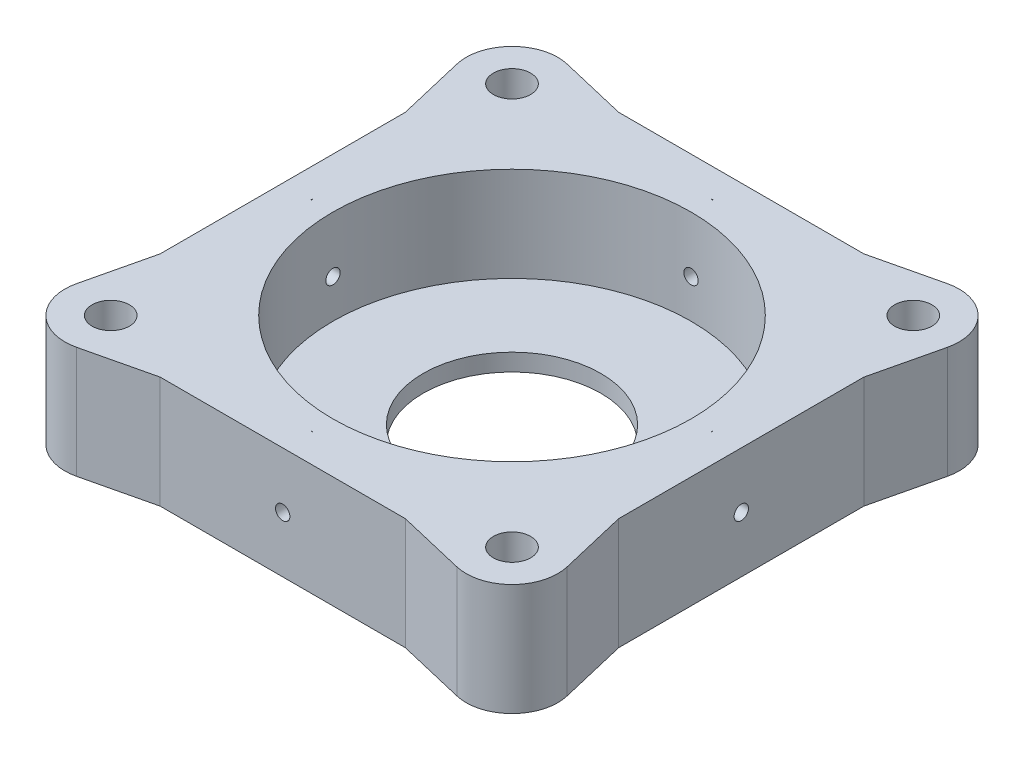
SolidWorks part; units mm, degrees
ref_plane "Front Plane" through (0, 0, 0) normal (0, 0, 1) x (1, 0, 0)
ref_plane "Top Plane" through (0, 0, 0) normal (0, 1, 0) x (1, 0, 0)
ref_plane "Right Plane" through (0, 0, 0) normal (1, 0, 0) x (0, 0, -1)
sketch "Sketch1" plane through (0, 0, 0) normal (0, 1, 0) x (1, 0, 0)
  line L0 (0, 35) -> (0, -35) construction
  line L1 (35, -35) -> (-35, -35)
  line L2 (35, -35) -> (35, 35)
  line L3 (35, 35) -> (-35, 35)
  line L4 (-35, -35) -> (-35, 35)
  line L5 (35, -35) -> (-35, 35) construction
  line L6 (35, 35) -> (-35, -35) construction
  line L7 (-35, 0) -> (35, 0) construction
  line L8 (-33.1578, 42.785) -> (7.8292, 33.0863)
  line L9 (-42.785, 33.1578) -> (-33.0863, -7.8292)
  line L10 (42.785, 33.1578) -> (33.0863, -7.8292)
  line L11 (33.1578, 42.785) -> (-7.8292, 33.0863)
  line L12 (-42.785, -33.1578) -> (-33.0863, 7.8292)
  line L13 (-33.1578, -42.785) -> (7.8292, -33.0863)
  line L14 (33.1578, -42.785) -> (-7.8292, -33.0863)
  line L15 (42.785, -33.1578) -> (33.0863, 7.8292)
  line L17 (40, -40) -> (-40, -40)
  line L18 (40, -40) -> (40, 40)
  line L19 (40, 40) -> (-40, 40)
  line L20 (-40, -40) -> (-40, 40)
  line L21 (40, -40) -> (-40, 40) construction
  line L22 (40, 40) -> (-40, -40) construction
  circle A0 centre (0, 0) radius 15.5
  circle A1 centre (0, 0) radius 34
  circle A2 centre (-35, 35) radius 3.25
  circle A3 centre (0, 0) radius 40
  circle A4 centre (-35, 35) radius 8
  circle A5 centre (35, 35) radius 3.25
  circle A6 centre (35, 35) radius 8
  circle A7 centre (-35, -35) radius 3.25
  circle A8 centre (-35, -35) radius 8
  circle A9 centre (35, -35) radius 3.25
  circle A10 centre (35, -35) radius 8
  dimension "D1" = 31
  dimension "D2" = 68
  dimension "D3" = 6.5
  dimension "D5" = 80
  dimension "D4" = 16
  dimension "D6" = 70
extrude "Boss-Extrude1" add sketch "Sketch1" along normal blind 19.5 contours L19 A4 L20 | L3 A4 L19 L20 L4 A2 | L4 A4 L3 A2 | A4 L9 L20 | A4 L20 L9 A3 L4 | A3 L9 L20 | L4 A3 L9 | L9 A3 L12 L4 | A3 L20 L12 | L12 A3 L4 | L20 A8 L4 A3 L12 | L12 A8 L20 | A8 L17 L20 | A8 L20 L17 L1 A7 L4 | A8 L4 A7 L1 | L4 A8 L1 A3 | L4 A3 L1 L13 L14 A1 L9 L12 | L3 A3 L4 L9 L12 A1 L11 L8 | A1 L12 L9 | A4 L4 A3 L3 | A4 L3 A3 L8 L19 | A4 L19 L8 | A3 L19 L8 | L8 A3 L3 | L11 A3 L8 L3 | A1 L8 L11 | L3 A3 L11 | L2 A3 L3 L11 L8 A1 L15 L10 | L3 A6 L19 L11 A3 | A3 L11 L19 | L19 A6 L11 | L2 A6 L3 A3 | A6 L2 A5 L3 | A6 L3 A5 L2 L18 L19 | A6 L19 L18 | L10 A6 L18 | L18 A6 L2 A3 L10 | A3 L18 L10 | L10 A3 L2 | L15 A3 L10 L2 | A3 L15 L18 | L2 A3 L15 | A1 L10 L15 | L1 A3 L2 L15 L10 A1 L13 L14 | A10 L18 L15 A3 L2 | A10 L15 L18 | A10 L2 A3 L1 | L18 A10 L2 A9 L1 L17 | L2 A10 L1 A9 | A10 L18 L17 | A10 L17 L14 | A10 L1 A3 L14 L17 | L14 A3 L1 | A3 L17 L14 | A3 L14 L1 L13 | A1 L14 L13 | L1 A3 L13 | A3 L13 L17 | L1 A8 L17 L13 A3 | L17 A8 L13 | A1 A0 region at (-27.625, 0, 37.5886) region at (-28.9419, 0, 28.9419) region at (-31.2062, 0, 31.2062) region at (-21.8672, 0, 37.555) region at (-24.6184, 0, 24.6184) region at (-10.9152, 0, 35.995) region at (-37.555, 0, 21.8672) region at (-30.8311, 0, 41.5907) region at (-27.2274, 0, 40.8217) region at (0, 0, 37.8149) region at (-35.995, 0, 10.9152) region at (-12.614, 0, 39.3478) region at (-40.8217, 0, 27.2274) region at (24.6184, 0, 24.6184) region at (10.9152, 0, 35.995) region at (0, 0, 34.191) region at (-37.8149, 0, 0) region at (-39.3478, 0, 12.614) region at (12.614, 0, 39.3478) region at (28.9419, 0, 28.9419) region at (21.8672, 0, 37.555) region at (0, 0, 33.0383) region at (-35.995, 0, -10.9152) region at (-24.6184, 0, -24.6184) region at (-34.191, 0, 0) region at (-39.3478, 0, -12.614) region at (27.2274, 0, 40.8217) region at (31.2062, 0, 31.2062) region at (29.375, 0, 35.1838) region at (37.555, 0, 21.8672) region at (35.995, 0, 10.9152) region at (34.191, 0, 0) region at (-37.555, 0, -21.8672) region at (-28.9419, 0, -28.9419) region at (-40.8217, 0, -27.2274) region at (30.8311, 0, 41.5907) region at (37.8149, 0, 0) region at (39.3478, 0, 12.614) region at (24.6184, 0, -24.6184) region at (-37.5886, 0, -27.625) region at (-31.2062, 0, -31.2062) region at (-10.9152, 0, -35.995) region at (-21.8672, 0, -37.555) region at (0, 0, -34.191) region at (-40.5144, 0, -40.5144) region at (40.8217, 0, 27.2274) region at (35.995, 0, -10.9152) region at (39.3478, 0, -12.614) region at (0, 0, -37.8149) region at (-12.614, 0, -39.3478) region at (-27.2274, 0, -40.8217) region at (28.9419, 0, -28.9419) region at (37.555, 0, -21.8672) region at (40.8217, 0, -27.2274) region at (10.9152, 0, -35.995) region at (12.614, 0, -39.3478) region at (31.2062, 0, -31.2062) region at (35.1838, 0, -29.375) region at (21.8672, 0, -37.555) region at (41.5907, 0, -30.8311)
sketch "Sketch2" plane through (0, 19.5, 0) normal (0, 1, 0) x (1, 0, 0)
  circle A0 centre (0, 0) radius 31.25
  dimension "D1" = 62.5
extrude "Cut-Extrude1" cut sketch "Sketch2" against normal blind 16.5
sketch "Sketch3" plane through (0, 0, 0) normal (0, -1, 0) x (1, 0, 0)
  circle A0 centre (-35, 35) radius 5.25
  circle A1 centre (35, 35) radius 5.25
  circle A2 centre (35, -35) radius 5.25
  circle A3 centre (-35, -35) radius 5.25
  dimension "D1" = 10.5
extrude "Cut-Extrude2" cut sketch "Sketch3" against normal blind 6
sketch "Sketch4" plane through (0, 0, 40) normal (0, 0, 1) x (1, 0, 0)
  line L0 (0, 0) -> (0, 19.5) construction
  line L1 (21.3883, 0) -> (-21.3883, 0) construction
  line L2 (21.3883, 19.5) -> (-21.3883, 19.5) construction
  circle A0 centre (0, 9.75) radius 1.25
  dimension "D1" = 2.5
extrude "Cut-Extrude3" cut sketch "Sketch4" against normal up to surface (80 mm away) up to face at (0, 9.75, -40)
sketch "Sketch5" plane through (40, 0, 0) normal (1, 0, 0) x (0, 0, -1)
  line L0 (0, 0) -> (0, 19.5) construction
  line L1 (-21.3883, 19.5) -> (21.3883, 19.5) construction
  circle A0 centre (0, 9.75) radius 1.25
  dimension "D1" = 2.5
extrude "Cut-Extrude4" cut sketch "Sketch5" against normal up to surface (80 mm away) up to face at (-40, 9.75, 0)
sketch "Sketch6" [suppressed] plane through (0, 19.5, 0) normal (0, 1, 0) x (1, 0, 0)
  line L12 (21.3883, -40) -> (33.1578, -42.785)
  line L13 (42.785, -33.1578) -> (40, -21.3883)
  line L14 (40, -21.3883) -> (40, 21.3883)
  line L15 (40, 21.3883) -> (42.785, 33.1578)
  line L16 (33.1578, 42.785) -> (21.3883, 40)
  line L17 (21.3883, 40) -> (-21.3883, 40)
  line L18 (-21.3883, 40) -> (-33.1578, 42.785)
  line L19 (-42.785, 33.1578) -> (-40, 21.3883)
  line L20 (-40, 21.3883) -> (-40, -21.3883)
  line L21 (-40, -21.3883) -> (-42.785, -33.1578)
  line L22 (-33.1578, -42.785) -> (-21.3883, -40)
  line L23 (-21.3883, -40) -> (21.3883, -40)
  line L24 (21.3883, -40) -> (33.1578, -42.785)
  line L25 (42.785, -33.1578) -> (40, -21.3883)
  line L26 (40, -21.3883) -> (40, 21.3883)
  line L27 (40, 21.3883) -> (42.785, 33.1578)
  line L28 (33.1578, 42.785) -> (21.3883, 40)
  line L29 (21.3883, 40) -> (-21.3883, 40)
  line L30 (-21.3883, 40) -> (-33.1578, 42.785)
  line L31 (-42.785, 33.1578) -> (-40, 21.3883)
  line L32 (-40, 21.3883) -> (-40, -21.3883)
  line L33 (-40, -21.3883) -> (-42.785, -33.1578)
  line L34 (-33.1578, -42.785) -> (-21.3883, -40)
  line L35 (-21.3883, -40) -> (21.3883, -40)
  circle A0 centre (0, 0) radius 31.25 construction
  circle A1 centre (35, 35) radius 3.25 construction
  circle A2 centre (-35, 35) radius 3.25 construction
  circle A3 centre (35, -35) radius 3.25 construction
  arc A4 (33.1578, -42.785) -> (42.785, -33.1578) centre (35, -35) ccw
  arc A5 (42.785, 33.1578) -> (33.1578, 42.785) centre (35, 35) ccw
  arc A6 (-33.1578, 42.785) -> (-42.785, 33.1578) centre (-35, 35) ccw
  arc A7 (-42.785, -33.1578) -> (-33.1578, -42.785) centre (-35, -35) ccw
  arc A8 (33.1578, -42.785) -> (42.785, -33.1578) centre (35, -35) ccw
  arc A9 (42.785, 33.1578) -> (33.1578, 42.785) centre (35, 35) ccw
  arc A10 (-33.1578, 42.785) -> (-42.785, 33.1578) centre (-35, 35) ccw
  arc A11 (-42.785, -33.1578) -> (-33.1578, -42.785) centre (-35, -35) ccw
  circle A12 centre (-35, -35) radius 3.25 construction
  circle A13 centre (0, 0) radius 31.25
  circle A14 centre (35, 35) radius 3.25
  circle A15 centre (-35, 35) radius 3.25
  circle A16 centre (35, -35) radius 3.25
  circle A17 centre (-35, -35) radius 3.25
  dimension "D1" = 0
extrude "Boss-Extrude4" [suppressed] add sketch "Sketch6" along normal blind 3.5
sketch "Sketch7" [suppressed] plane through (0, 0, 0) normal (0, -1, 0) x (1, 0, 0)
  line L0 (-35, 35) -> (-38.7123, 38.7123) construction
  line L1 (-29.1444, 33.431) -> (-30.7134, 39.2866)
  line L2 (-30.7134, 39.2866) -> (-36.569, 40.8556)
  line L3 (-36.569, 40.8556) -> (-40.8556, 36.569)
  line L4 (-40.8556, 36.569) -> (-39.2866, 30.7134)
  line L5 (-39.2866, 30.7134) -> (-33.431, 29.1444)
  line L6 (-33.431, 29.1444) -> (-29.1444, 33.431)
  line L7 (39.2866, 30.7134) -> (40.8556, 36.569)
  line L8 (40.8556, 36.569) -> (36.569, 40.8556)
  line L9 (36.569, 40.8556) -> (30.7134, 39.2866)
  line L10 (30.7134, 39.2866) -> (29.1444, 33.431)
  line L11 (29.1444, 33.431) -> (33.431, 29.1444)
  line L12 (33.431, 29.1444) -> (39.2866, 30.7134)
  line L13 (30.7134, -39.2866) -> (36.569, -40.8556)
  line L14 (36.569, -40.8556) -> (40.8556, -36.569)
  line L15 (40.8556, -36.569) -> (39.2866, -30.7134)
  line L16 (39.2866, -30.7134) -> (33.431, -29.1444)
  line L17 (33.431, -29.1444) -> (29.1444, -33.431)
  line L18 (29.1444, -33.431) -> (30.7134, -39.2866)
  line L19 (-39.2866, -30.7134) -> (-40.8556, -36.569)
  line L20 (-40.8556, -36.569) -> (-36.569, -40.8556)
  line L21 (-36.569, -40.8556) -> (-30.7134, -39.2866)
  line L22 (-30.7134, -39.2866) -> (-29.1444, -33.431)
  line L23 (-29.1444, -33.431) -> (-33.431, -29.1444)
  line L24 (-33.431, -29.1444) -> (-39.2866, -30.7134)
  line L25 (0, 40) -> (0, -40) construction
  line L26 (21.3883, 40) -> (-21.3883, 40) construction
  line L27 (21.3883, -40) -> (-21.3883, -40) construction
  circle A0 centre (-35, 35) radius 5.25 construction
  point P32 (0, 0)
  dimension "D1" = 10.5
  dimension "D2" = 4
extrude "Cut-Extrude5" [suppressed] cut sketch "Sketch7" against normal offset from surface (21.5 mm away) 1.5 up to face at (35, 0, 29.75)
